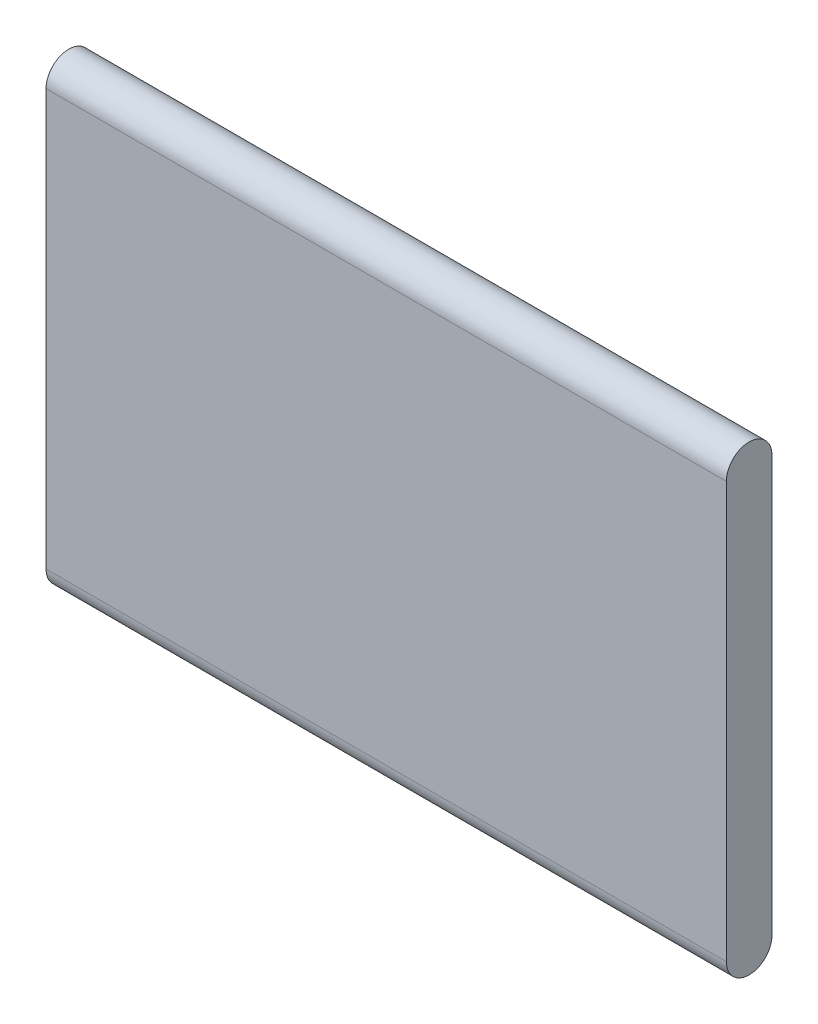
SolidWorks part; units mm, degrees
ref_plane "Front Plane" through (0, 0, 0) normal (0, 0, 1) x (1, 0, 0)
ref_plane "Top Plane" through (0, 0, 0) normal (0, 1, 0) x (1, 0, 0)
ref_plane "Right Plane" through (0, 0, 0) normal (1, 0, 0) x (0, 0, -1)
sketch "Sketch1" plane through (0, 0, 0) normal (1, 0, 0) x (0, 0, -1)
  line L0 (-23.8125, 217.4875) -> (23.8125, -217.4875) construction
  line L2 (-23.8125, 217.4875) -> (-23.8125, -217.4875)
  line L4 (23.8125, 217.4875) -> (23.8125, -217.4875)
  arc A0 (23.8125, 217.4875) -> (-23.8125, 217.4875) centre (0, 217.4875) ccw
  arc A1 (-23.8125, -217.4875) -> (23.8125, -217.4875) centre (0, -217.4875) ccw
  dimension "D1" = 23.8125
  dimension "D2" = 482.6
extrude "Boss-Extrude1" add sketch "Sketch1" along normal mid plane 711.2
